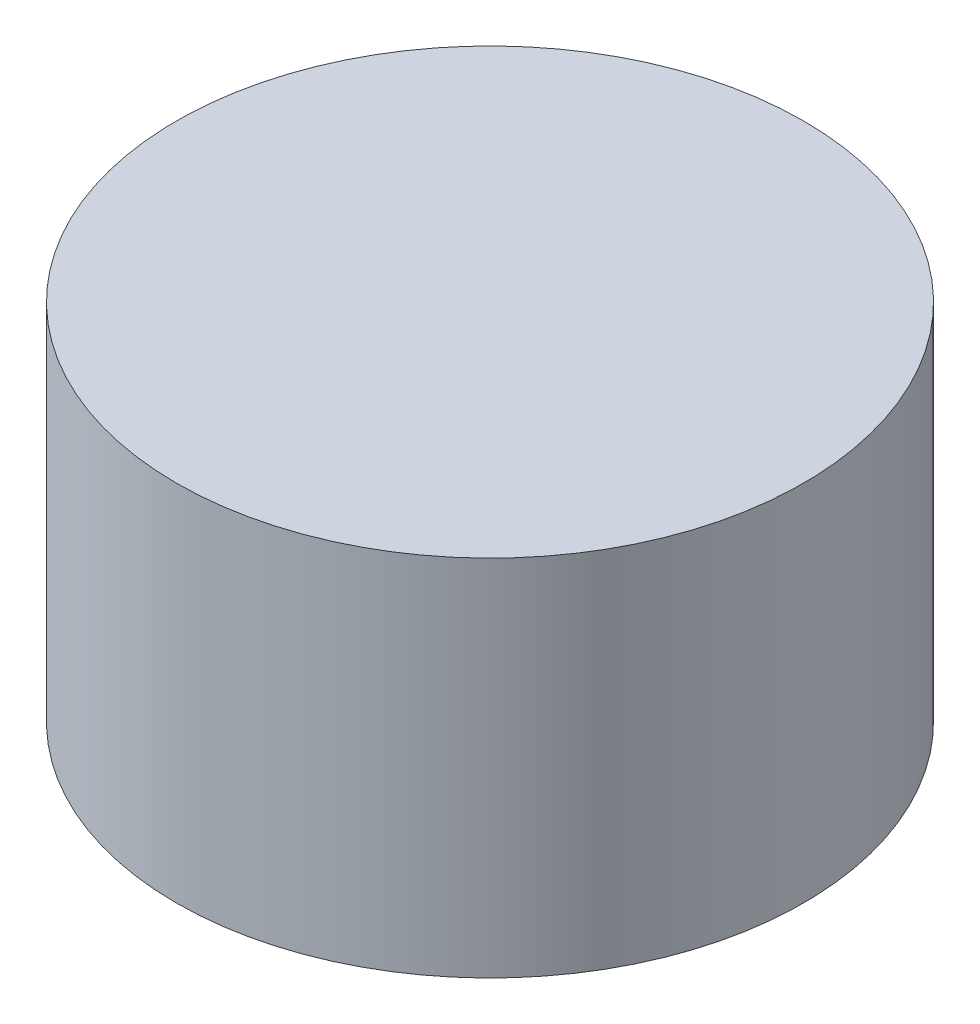
SolidWorks part; units mm, degrees
ref_plane "Front Plane" through (0, 0, 0) normal (0, 0, 1) x (1, 0, 0)
ref_plane "Top Plane" through (0, 0, 0) normal (0, 1, 0) x (1, 0, 0)
ref_plane "Right Plane" through (0, 0, 0) normal (1, 0, 0) x (0, 0, -1)
sketch "Sketch1" plane through (0, 0, 0) normal (0, 1, 0) x (1, 0, 0)
  circle A0 centre (0, 0) radius 17.25
  dimension "D1" = 34.5
extrude "Boss-Extrude1" add sketch "Sketch1" along normal blind 20
ref_plane "Plane1" through (0, 10, 0) normal (0, -1, 0) x (-1, 0, 0)
ref_axis "Axis1" through (0, 20, 0) along (0, -1, 0)
